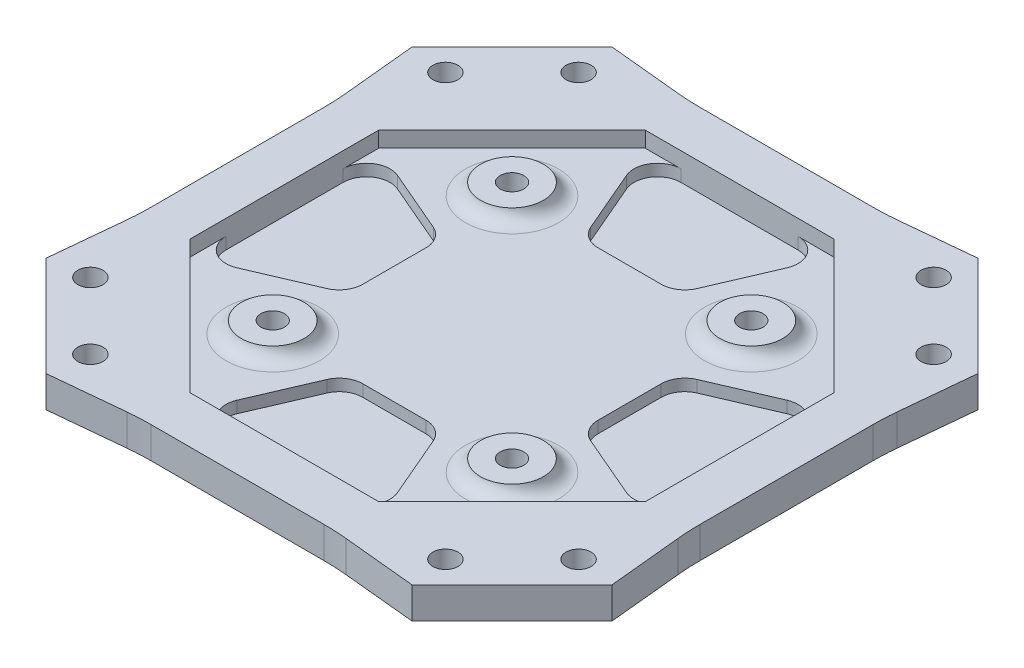
SolidWorks part; units mm, degrees
ref_plane "Front Plane" through (0, 0, 0) normal (0, 0, 1) x (1, 0, 0)
ref_plane "Top Plane" through (0, 0, 0) normal (0, 1, 0) x (1, 0, 0)
ref_plane "Right Plane" through (0, 0, 0) normal (1, 0, 0) x (0, 0, -1)
sketch "Sketch2" plane through (0, 0, 0) normal (0, 1, 0) x (1, 0, 0)
  line L0 (0, 0) -> (84.8528, 84.8528) construction
  line L1 (-35, -35) -> (35, -35) construction
  line L2 (-35, -35) -> (-35, 35) construction
  line L3 (-35, 35) -> (35, 35) construction
  line L4 (35, -35) -> (35, 35) construction
  line L5 (-35, -35) -> (35, 35) construction
  line L6 (-35, 35) -> (35, -35) construction
  line L7 (0, 35) -> (0, -35) construction
  line L8 (-12.5, 35) -> (12.5, 35)
  line L9 (35, 12.5) -> (35, -12.5)
  line L10 (12.5, -35) -> (-12.5, -35)
  line L11 (-35, -12.5) -> (-35, 12.5)
  line L12 (20.5061, 33.234) -> (33.234, 20.5061) construction
  line L13 (23.3345, 36.0624) -> (36.0624, 23.3345)
  line L14 (12.5, 35) -> (23.3345, 36.0624)
  line L15 (35, 12.5) -> (36.0624, 23.3345)
  line L16 (35, -12.5) -> (36.0624, -23.3345)
  line L17 (36.0624, -23.3345) -> (23.3345, -36.0624)
  line L18 (12.5, -35) -> (23.3345, -36.0624)
  line L19 (-12.5, -35) -> (-23.3345, -36.0624)
  line L20 (-23.3345, -36.0624) -> (-36.0624, -23.3345)
  line L21 (-35, -12.5) -> (-36.0624, -23.3345)
  line L22 (-35, 12.5) -> (-36.0624, 23.3345)
  line L23 (-36.0624, 23.3345) -> (-23.3345, 36.0624)
  line L24 (-12.5, 35) -> (-23.3345, 36.0624)
  circle A0 centre (22.6274, 31.1127) radius 1.6
  circle A1 centre (31.1127, 22.6274) radius 1.6
  circle A2 centre (22.6274, -31.1127) radius 1.6
  circle A3 centre (31.1127, -22.6274) radius 1.6
  circle A4 centre (-31.1127, -22.6274) radius 1.6
  circle A5 centre (-22.6274, -31.1127) radius 1.6
  circle A6 centre (-22.6274, 31.1127) radius 1.6
  circle A7 centre (-31.1127, 22.6274) radius 1.6
  point P0 (0, 0)
  point P13 (0, 35)
  point P22 (0, 0)
  point P23 (42.4264, 42.4264)
  point P25 (26.8701, 26.8701)
  point P27 (29.6985, 29.6985)
  point P58 (0, 0)
  dimension "D6" = 3.2
  dimension "D10" = 6
  dimension "D1" = 70
  dimension "D2" = 70
  dimension "D3" = 120
  dimension "D4" = 25
  dimension "D5" = 4
  dimension "D7" = 82
  dimension "D8" = 4
  dimension "D9" = 18
  dimension "D11" = 6
  dimension "D12" = 4
extrude "Boss-Extrude1" add sketch "Sketch2" along normal blind 4
sketch "Sketch4" plane through (0, 4, 0) normal (0, 1, 0) x (1, 0, 0)
  line L0 (12.5, 35) -> (-12.5, 35) construction
  line L1 (29, 12.0122) -> (12.0122, 29)
  line L2 (12.0122, 29) -> (-12.0122, 29)
  line L3 (-12.0122, 29) -> (-29, 12.0122)
  line L4 (-29, 12.0122) -> (-29, -12.0122)
  line L5 (-29, -12.0122) -> (-12.0122, -29)
  line L6 (-12.0122, -29) -> (12.0122, -29)
  line L7 (12.0122, -29) -> (29, -12.0122)
  line L8 (29, -12.0122) -> (29, 12.0122)
  line L9 (-35, 12.5) -> (-35, -12.5) construction
  line L11 (-36.0624, -23.3345) -> (-23.3345, -36.0624) construction
  circle A0 centre (0, 0) radius 29 construction
  dimension "D1" = 6
  dimension "D2" = 13
extrude "Cut-Extrude1" cut sketch "Sketch4" against normal blind 2
sketch "Sketch5" plane through (0, 2, 0) normal (0, 1, 0) x (1, 0, 0)
  line L0 (0, 29) -> (0, 0) construction
  line L1 (12.0122, 29) -> (-12.0122, 29) construction
  line L2 (0, 0) -> (-29, 0) construction
  line L3 (-29, 12.0122) -> (-29, -12.0122) construction
  line L4 (-24.8162, 10.2155) -> (-16.8162, 6.78)
  line L5 (-15, 4.0234) -> (-15, -4.0234)
  line L6 (-16.8162, -6.78) -> (-24.8162, -10.2155)
  line L7 (-29, -7.4589) -> (-29, 7.4589)
  line L8 (10.2155, 24.8162) -> (6.78, 16.8162)
  line L9 (-7.4589, 29) -> (7.4589, 29)
  line L10 (-6.78, 16.8162) -> (-10.2155, 24.8162)
  line L11 (4.0234, 15) -> (-4.0234, 15)
  line L12 (24.8162, -10.2155) -> (16.8162, -6.78)
  line L13 (29, 7.4589) -> (29, -7.4589)
  line L14 (16.8162, 6.78) -> (24.8162, 10.2155)
  line L15 (15, -4.0234) -> (15, 4.0234)
  line L16 (-10.2155, -24.8162) -> (-6.78, -16.8162)
  line L17 (7.4589, -29) -> (-7.4589, -29)
  line L18 (6.78, -16.8162) -> (10.2155, -24.8162)
  line L19 (-4.0234, -15) -> (4.0234, -15)
  arc A0 (-16.8162, 6.78) -> (-15, 4.0234) centre (-18, 4.0234) cw
  arc A1 (-15, -4.0234) -> (-16.8162, -6.78) centre (-18, -4.0234) cw
  arc A2 (-24.8162, -10.2155) -> (-29, -7.4589) centre (-26, -7.4589) cw
  arc A3 (-24.8162, 10.2155) -> (-29, 7.4589) centre (-26, 7.4589) ccw
  arc A4 (-10.2155, 24.8162) -> (-7.4589, 29) centre (-7.4589, 26) cw
  arc A5 (-4.0234, 15) -> (-6.78, 16.8162) centre (-4.0234, 18) cw
  arc A6 (6.78, 16.8162) -> (4.0234, 15) centre (4.0234, 18) cw
  arc A7 (10.2155, 24.8162) -> (7.4589, 29) centre (7.4589, 26) ccw
  arc A8 (24.8162, 10.2155) -> (29, 7.4589) centre (26, 7.4589) cw
  arc A9 (15, 4.0234) -> (16.8162, 6.78) centre (18, 4.0234) cw
  arc A10 (16.8162, -6.78) -> (15, -4.0234) centre (18, -4.0234) cw
  arc A11 (24.8162, -10.2155) -> (29, -7.4589) centre (26, -7.4589) ccw
  arc A12 (10.2155, -24.8162) -> (7.4589, -29) centre (7.4589, -26) cw
  arc A13 (4.0234, -15) -> (6.78, -16.8162) centre (4.0234, -18) cw
  arc A14 (-6.78, -16.8162) -> (-4.0234, -15) centre (-4.0234, -18) cw
  arc A15 (-10.2155, -24.8162) -> (-7.4589, -29) centre (-7.4589, -26) ccw
  point P17 (-15, 6)
  point P20 (-15, -6)
  point P23 (-29, -12.0122)
  point P26 (-29, 12.0122)
  point P65 (0, 0)
  dimension "D3" = 3
  dimension "D1" = 15
  dimension "D2" = 12
  dimension "D4" = 4
extrude "Cut-Extrude2" cut sketch "Sketch5" against normal blind 1.5
sketch "Sketch6" plane through (0, 2, 0) normal (0, 1, 0) x (1, 0, 0)
  line L1 (0, 0) -> (15.25, 0) construction
  line L2 (0, 0) -> (0, 15.25) construction
  line L3 (0, 15.25) -> (15.25, 15.25) construction
  line L4 (15.25, 0) -> (15.25, 15.25) construction
  circle A0 centre (15.25, 15.25) radius 1.5
  dimension "D2" = 3
  dimension "D1" = 15.25
extrude "Cut-Extrude3" cut sketch "Sketch6" against normal through all
sketch "Sketch7" plane through (0, 2, 0) normal (0, 1, 0) x (1, 0, 0)
  circle A0 centre (15.25, 15.25) radius 4
  circle A1 centre (15.25, 15.25) radius 1.5 construction
  circle A2 centre (15.25, 15.25) radius 1.5
  dimension "D1" = 8
extrude "Boss-Extrude4" add sketch "Sketch7" along normal blind 1.5
ref_axis "Axis1" through (0, 4.2, 0) along (0, -1, 0)
pattern_circular "CirPattern1" count 4 over 360 about axis through (0, 4.2, 0) along (0, -1, 0) of "Boss-Extrude4", "Cut-Extrude3"
fillet "Fillet2" radius 2 4 edges at (15.25, 2, -11.25) (-11.25, 2, -15.25) (-15.25, 2, 11.25) (11.25, 2, 15.25)
fillet "Fillet4" radius 30 8 edges at (-35, 2, -12.5) (-35, 2, 12.5) (-12.5, 2, -35) (12.5, 2, -35) (35, 2, -12.5) (35, 2, 12.5) (12.5, 2, 35) (-12.5, 2, 35)
